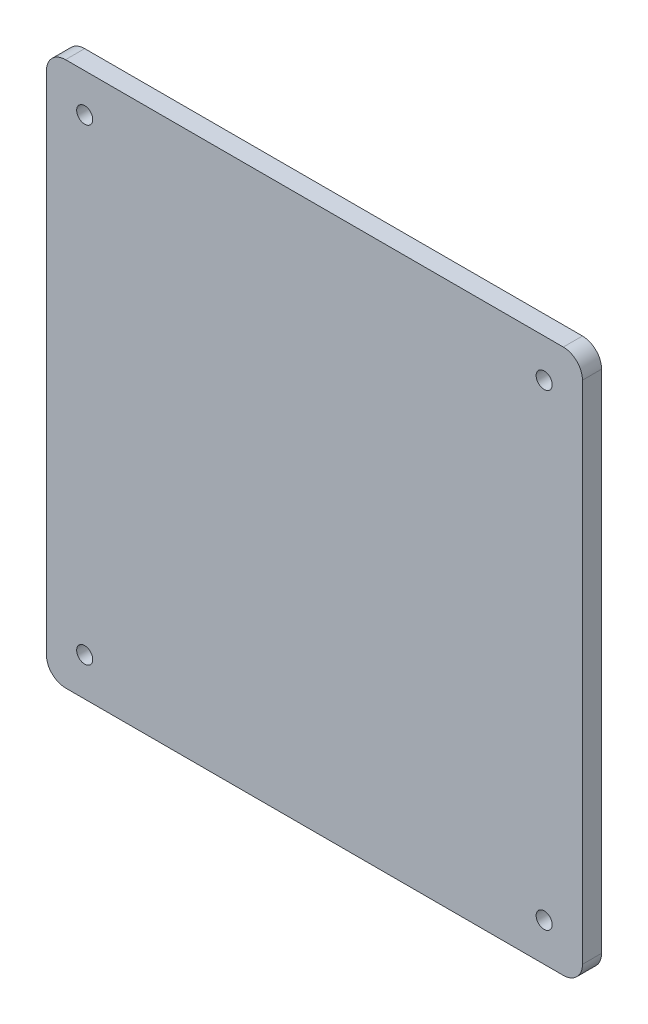
SolidWorks part; units mm, degrees
ref_plane "前视基准面" through (0, 0, 0) normal (0, 0, 1) x (1, 0, 0)
ref_plane "上视基准面" through (0, 0, 0) normal (0, 1, 0) x (1, 0, 0)
ref_plane "右视基准面" through (0, 0, 0) normal (1, 0, 0) x (0, 0, -1)
sketch "草图1" plane through (0, 0, 0) normal (0, 0, 1) x (1, 0, 0)
  line L5 (-140, -142.125) -> (140, -142.125)
  line L6 (-140, -142.125) -> (-140, 142.125)
  line L7 (-140, 142.125) -> (140, 142.125)
  line L8 (140, -142.125) -> (140, 142.125)
  line L9 (-140, -142.125) -> (140, 142.125) construction
  line L10 (-140, 142.125) -> (140, -142.125) construction
  point P0 (0, 0)
  dimension "D1" = 280
  dimension "D2" = 284.25
extrude "凸台-拉伸1" add sketch "草图1" along normal blind 10
fillet "圆角1" radius 10 4 edges at (140, -142.125, 5) (-140, -142.125, 5) (-140, 142.125, 5) (140, 142.125, 5)
hole_wizard "Ø8.4 (8.4) 直径孔1" positions "草图2" profile "草图3" hole size "Ø8.4" standard "GB" end condition through all
sketch "草图2" plane through (0, 0, 0) normal (0, 0, 1) x (1, 0, 0)
  line L0 (130, 142.125) -> (-130, 142.125) construction
  line L1 (-140, 132.125) -> (-140, -132.125) construction
  line L2 (140, -132.125) -> (140, 132.125) construction
  line L3 (-130, -142.125) -> (130, -142.125) construction
  point P0 (-120, 122.125)
  point P3 (120, 122.125)
  point P6 (120, -122.125)
  point P9 (-120, -122.125)
  dimension "D1" = 20
  dimension "D2" = 20
  dimension "D3" = 20
  dimension "D4" = 20
  dimension "D5" = 20
  dimension "D6" = 20
  dimension "D7" = 20
  dimension "D8" = 20
sketch "草图3" plane through (-120, 122.125, 0) normal (1, 0, 0) x (0, 1, 0)
  line L0 (0, 0) -> (0, 10)
  line L1 (0, 10) -> (4.2, 10)
  line L2 (4.2, 10) -> (4.2, 0)
  line L5 (4.2, 0) -> (0, 0)
  line L11 (0, -6.35) -> (0, 107.95) construction
  dimension "通孔孔直径" = 8.4
  dimension "通孔孔深度" = 10
